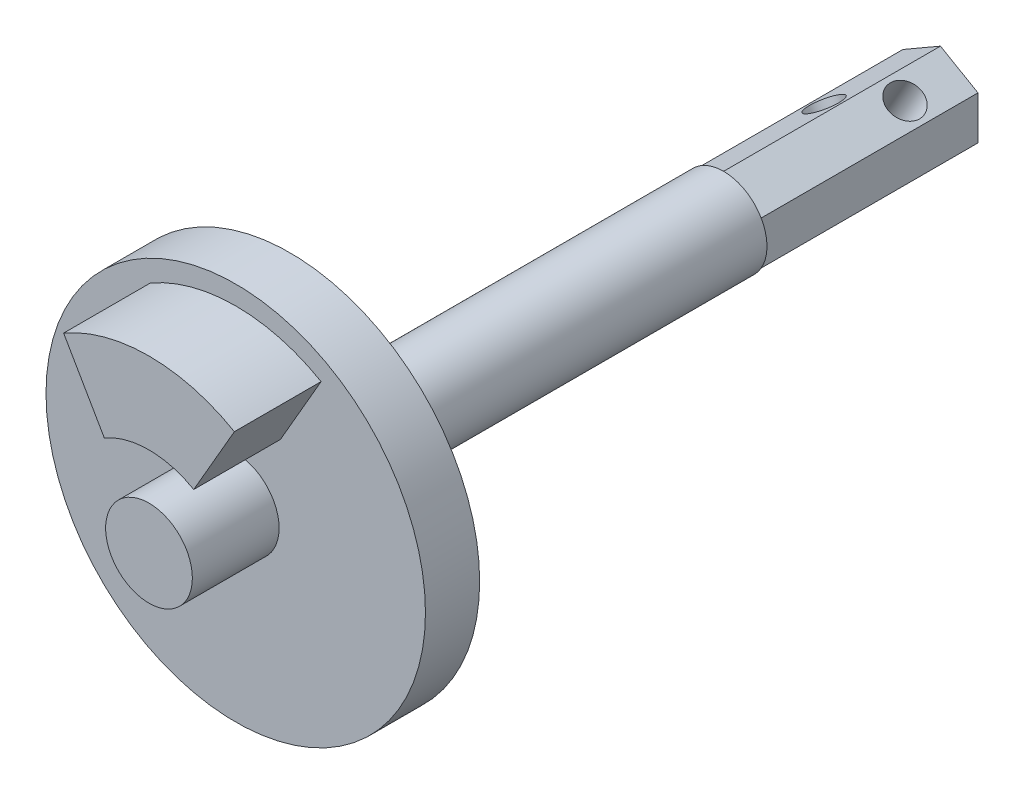
SolidWorks part; units mm, degrees
ref_plane "Front Plane" through (0, 0, 0) normal (0, 0, 1) x (1, 0, 0)
ref_plane "Top Plane" through (0, 0, 0) normal (0, 1, 0) x (1, 0, 0)
ref_plane "Right Plane" through (0, 0, 0) normal (1, 0, 0) x (0, 0, -1)
sketch "Sketch1" plane through (0, 0, 0) normal (0, 0, 1) x (1, 0, 0)
  circle A0 centre (0, 0) radius 17.5
  dimension "D1" = 35
extrude "Boss-Extrude1" add sketch "Sketch1" along normal mid plane 5
sketch "Sketch2" plane through (0, 0, 2.5) normal (0, 0, 1) x (1, 0, 0)
  line L3 (0, 0) -> (0, 11) construction
  line L4 (7.875, 13.6399) -> (4.125, 7.1447)
  line L5 (-4.125, 7.1447) -> (-7.875, 13.6399)
  arc A1 (4.125, 7.1447) -> (-4.125, 7.1447) centre (0, 0) ccw
  arc A6 (-7.875, 13.6399) -> (7.875, 13.6399) centre (0, 0) cw
  circle A7 centre (0, 0) radius 17.5 construction
  dimension "D2" = 7.5
  dimension "D3" = 1.75
  dimension "D1" = 30
extrude "Boss-Extrude2" add sketch "Sketch2" along normal blind 8
sketch "Sketch3" plane through (0, 0, 2.5) normal (0, 0, 1) x (1, 0, 0)
  circle A0 centre (0, 0) radius 4
extrude "Boss-Extrude3" add sketch "Sketch3" along normal blind 8
sketch "Sketch7" plane through (0, 0, -2.5) normal (0, 0, -1) x (-1, 0, 0)
  circle A0 centre (0, 0) radius 4
extrude "Boss-Extrude4" add sketch "Sketch7" along normal blind 40
sketch "Sketch9" plane through (0, 0, -42.5) normal (0, 0, -1) x (-1, 0, 0)
  line L0 (0, 4) -> (0, -4) construction
  line L1 (-3.4641, -2) -> (3.4641, 2) construction
  line L2 (-3.4641, 2) -> (3.4641, -2) construction
  line L11 (0, 4) -> (-3.4641, 2)
  line L12 (-3.4641, 2) -> (-3.4641, -2)
  line L13 (-3.4641, -2) -> (0, -4)
  line L14 (0, -4) -> (3.4641, -2)
  line L15 (3.4641, -2) -> (3.4641, 2)
  line L16 (3.4641, 2) -> (0, 4)
  circle A0 centre (0, 0) radius 4 construction
  point P4 (0, 0)
  point P5 (0, 0)
  point P6 (0, 0)
  point P8 (0, 0)
  point P11 (0, 0)
  point P13 (0, 0)
  point P15 (0, 0)
  point P19 (0, 0)
  point P22 (0, 0)
extrude "Boss-Extrude5" add sketch "Sketch9" along normal blind 20
sketch "Sketch10" plane through (-1.7321, -3, 0) normal (-0.5, -0.866, 0) x (0.866, -0.5, 0)
  line L2 (0, -57.5) -> (0, -42.5) construction
  line L3 (2, -42.5) -> (-2, -42.5) construction
  circle A0 centre (0, -57.5) radius 1.55
extrude "Cut-Extrude1" cut sketch "Sketch10" against normal up to surface (6.9282 mm away) up to face at (1.7321, 3, -52.5)
sketch "Sketch11" plane through (1.7321, -3, 0) normal (-0.5, 0.866, 0) x (0, 0, 1)
  line L0 (-53.5, 0) -> (-42.5, 0) construction
  line L1 (-42.5, 2) -> (-42.5, -2) construction
  circle A1 centre (-53.5, 0) radius 1.55
extrude "Cut-Extrude4" cut sketch "Sketch11" along normal up to surface (6.9282 mm away) up to face at (-1.7321, 3, -52.5)
